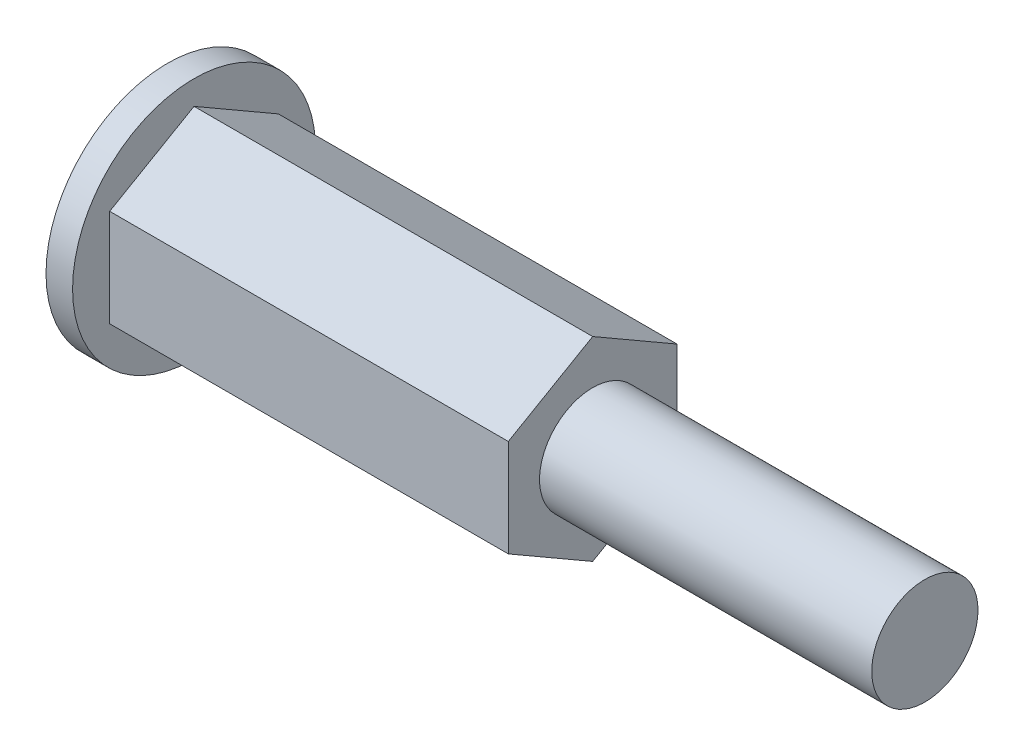
SolidWorks part; units mm, degrees
ref_plane "Front Plane" through (0, 0, 0) normal (1, 0, 0) x (0, 1, 0)
ref_plane "Top Plane" through (0, 0, 0) normal (0, 0, 1) x (0, 1, 0)
ref_plane "Right Plane" through (0, 0, 0) normal (0, 1, 0) x (-1, 0, 0)
sketch "Sketch1" plane through (0, 0, 0) normal (1, 0, 0) x (0, 1, 0)
  circle A0 centre (0, 0) radius 3.999
  dimension "D1" = 7.998
extrude "Boss-Extrude1" add sketch "Sketch1" along normal blind 55
sketch "Sketch2" plane through (0, 0, 0) normal (-1, 0, 0) x (0, -1, 0)
  circle A0 centre (0, 0) radius 9.141
  dimension "D1" = 18.282
extrude "Boss-Extrude2" add sketch "Sketch2" along normal blind 2
sketch "Sketch3" plane through (0, 0, 0) normal (1, 0, 0) x (0, 1, 0)
  line L1 (3.665, 6.348) -> (-3.665, 6.348)
  line L2 (-3.665, 6.348) -> (-7.33, 0)
  line L3 (-7.33, 0) -> (-3.665, -6.348)
  line L4 (-3.665, -6.348) -> (3.665, -6.348)
  line L5 (3.665, -6.348) -> (7.33, 0)
  line L6 (7.33, 0) -> (3.665, 6.348)
  circle A0 centre (0, 0) radius 6.348 construction
  dimension "D2" = 12.6959
  dimension "D1" = 7.33
extrude "Boss-Extrude3" add sketch "Sketch3" along normal blind 30
